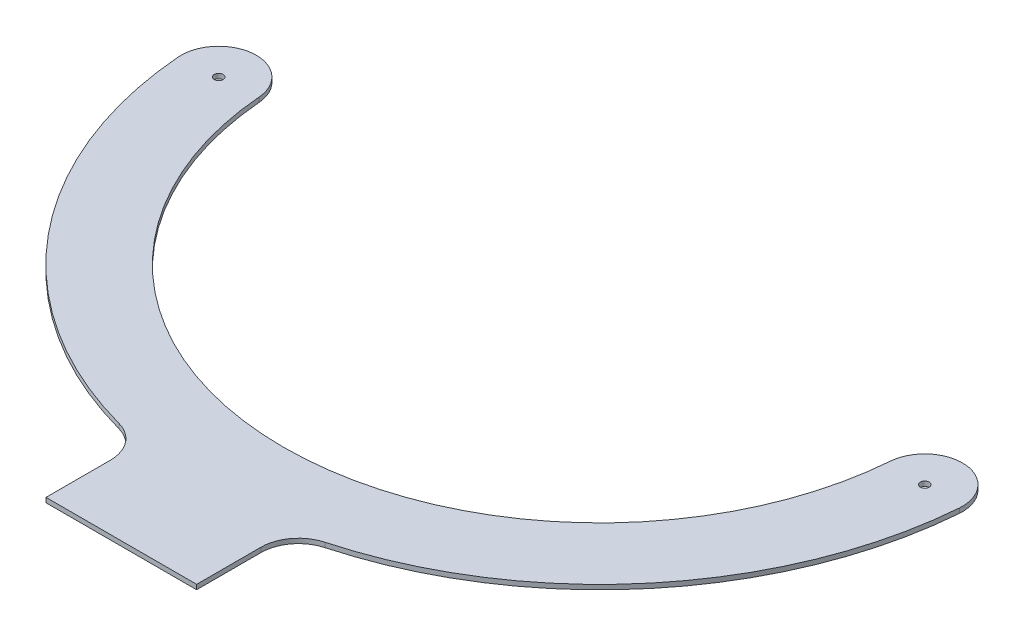
SolidWorks part; units mm, degrees
material "6061-T6 (SS)"
ref_plane "Front" through (0, 0, 0) normal (0, 0, 1) x (1, 0, 0)
ref_plane "Top" through (0, 0, 0) normal (0, 1, 0) x (1, 0, 0)
ref_plane "Right" through (0, 0, 0) normal (1, 0, 0) x (0, 0, -1)
sketch "Sketch1" plane through (0, 0, 0) normal (0, 1, 0) x (1, 0, 0)
  line L0 (50.8, 0) -> (-50.8, 0)
  line L1 (-50.8, 0) -> (-50.8, 63.5)
  line L2 (50.8, 0) -> (50.8, 63.5)
  circle A0 centre (0, 322.8575) radius 206.375 construction
  circle A1 centre (-238.125, 303.8075) radius 50.8 construction
  circle A2 centre (238.125, 303.8075) radius 50.8 construction
  arc A3 (-212.8059, 305.8331) -> (-263.4441, 301.782) centre (-238.125, 303.8075) ccw
  arc A4 (-212.8059, 305.8331) -> (212.8059, 305.8331) centre (0, 322.8575) ccw
  arc A5 (-263.4441, 301.782) -> (-50.8, 63.5) centre (0, 322.8575) ccw
  arc A6 (263.4441, 301.782) -> (212.8059, 305.8331) centre (238.125, 303.8075) ccw
  arc A7 (50.8, 63.5) -> (263.4441, 301.782) centre (0, 322.8575) ccw
  point P4 (0, 0)
  dimension "D1" = 412.75
  dimension "D2" = 101.6
  dimension "D3" = 19.05
  dimension "D4" = 25.4
  dimension "D5" = 19.05
  dimension "D6" = 63.5
  dimension "D7" = 101.6
extrude "Boss-Extrude1" add sketch "Sketch1" along normal blind 3.175
sketch "Sketch2" plane through (0, 3.175, 0) normal (0, 1, 0) x (1, 0, 0)
  circle A0 centre (-238.125, 303.8075) radius 3.008
  circle A1 centre (238.125, 303.8075) radius 3.008
  arc A2 (-212.8059, 305.8331) -> (-263.4441, 301.782) centre (-238.125, 303.8075) ccw construction
  arc A4 (263.4441, 301.782) -> (212.8059, 305.8331) centre (238.125, 303.8075) ccw construction
  dimension "D1" = 6.016
extrude "Cut-Extrude1" cut sketch "Sketch2" against normal through all
fillet "Fillet1" radius 25.4 2 edges at (50.8, 1.5875, -63.5) (-50.8, 1.5875, -63.5)
